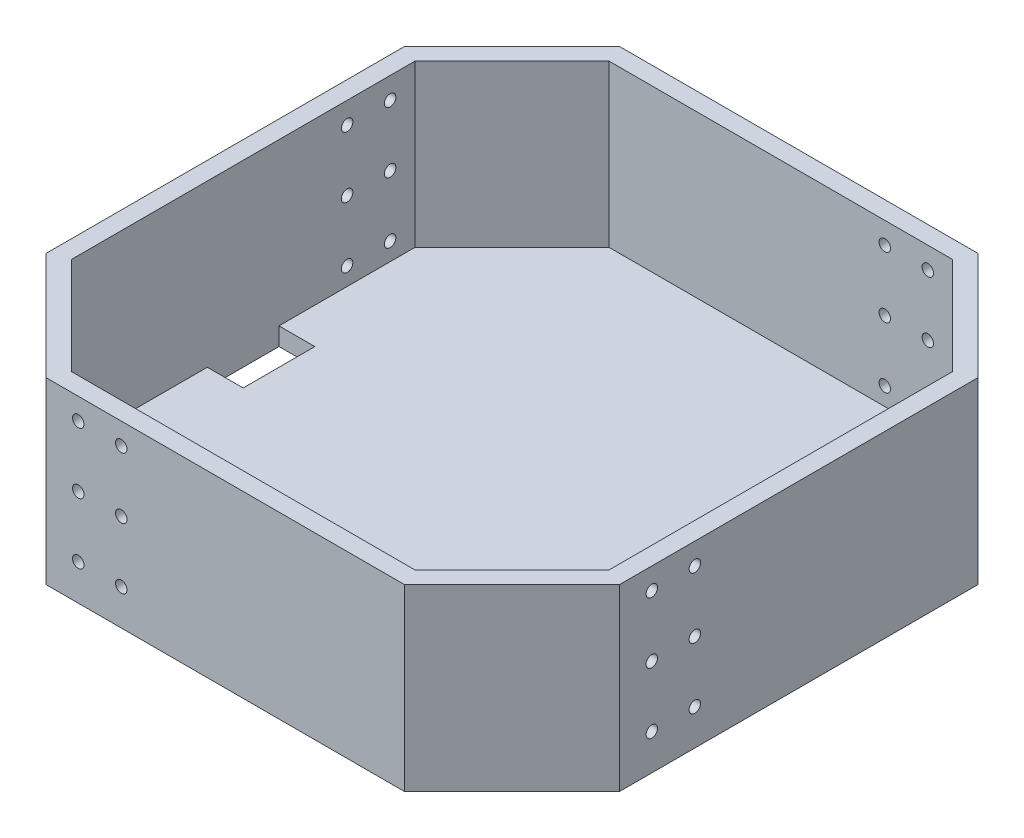
SolidWorks part; units mm, degrees
ref_plane "Front Plane" through (0, 0, 0) normal (0, 0, 1) x (1, 0, 0)
ref_plane "Top Plane" through (0, 0, 0) normal (0, 1, 0) x (1, 0, 0)
ref_plane "Right Plane" through (0, 0, 0) normal (1, 0, 0) x (0, 0, -1)
sketch "Sketch1" plane through (0, 0, 0) normal (0, 1, 0) x (1, 0, 0)
  line L0 (-80, 50) -> (-50, 80)
  line L1 (-80, 80) -> (80, 80)
  line L2 (-80, 80) -> (-80, -80)
  line L3 (-80, -80) -> (80, -80)
  line L4 (80, 80) -> (80, -80)
  line L5 (-80, 80) -> (80, -80) construction
  line L6 (-80, -80) -> (80, 80) construction
  line L7 (50, 80) -> (80, 50)
  line L8 (80, -50) -> (50, -80)
  line L9 (-50, -80) -> (-80, -50)
  point P0 (0, 0)
  point P8 (0, 0)
  point P11 (0, 0)
  point P14 (0, 0)
  point P17 (0, 0)
  point P20 (0, 0)
  dimension "D1" = 160
  dimension "D2" = 45
  dimension "D3" = 30
  dimension "D4" = 4
extrude "Boss-Extrude1" add sketch "Sketch1" along normal blind 50 contours L9 L3 L8 L4 L7 L1 L0 L2 region at (0, 0, 0)
shell "Shell1" thickness 5 removed face at (0, 50, 0)
sketch "Sketch5" plane through (0, 5, 0) normal (0, 1, 0) x (1, 0, 0)
  line L0 (-75, 47.9289) -> (-75, -47.9289) construction
  line L1 (-75, 10) -> (-65, 10)
  line L2 (-75, 10) -> (-75, -10)
  line L3 (-75, -10) -> (-65, -10)
  line L4 (-65, 10) -> (-65, -10)
  point P4 (-75, 0)
  point P7 (-75, 0)
  dimension "D1" = 20
  dimension "D2" = 10
extrude "Cut-Extrude1" cut sketch "Sketch5" against normal up to surface (5 mm away) up to face at (0, 0, 0)
sketch "Sketch6" plane through (0, 0, 80) normal (0, 0, 1) x (1, 0, 0)
  circle A0 centre (-29, 10) radius 1.6 construction
  circle A1 centre (-41, 10) radius 1.6 construction
  circle A2 centre (-29, 27) radius 1.6 construction
  circle A3 centre (-41, 27) radius 1.6 construction
  circle A4 centre (-29, 44) radius 1.6 construction
  circle A5 centre (-41, 44) radius 1.6 construction
  circle A6 centre (-29, 10) radius 1.6
  circle A7 centre (-41, 10) radius 1.6
  circle A8 centre (-29, 27) radius 1.6
  circle A9 centre (-41, 27) radius 1.6
  circle A10 centre (-29, 44) radius 1.6
  circle A11 centre (-41, 44) radius 1.6
extrude "Cut-Extrude2" cut sketch "Sketch6" against normal up to surface (5 mm away) up to face at (0, 27.5, 75)
ref_axis "Axis1" through (0, 52.5, 0) along (0, -1, 0)
pattern_circular "CirPattern1" count 4 every 90 about axis through (0, 52.5, 0) along (0, -1, 0) of "Cut-Extrude2"
